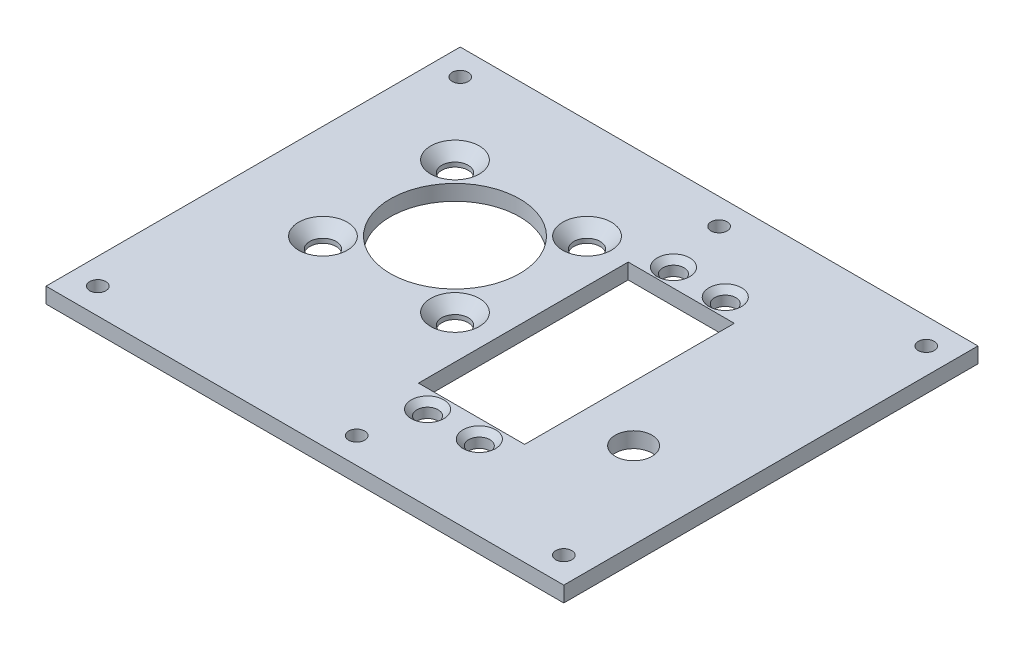
SolidWorks part; units mm, degrees
ref_plane "Płaszczyzna przednia" through (0, 0, 0) normal (0, 0, 1) x (1, 0, 0)
ref_plane "Płaszczyzna górna" through (0, 0, 0) normal (0, 1, 0) x (1, 0, 0)
ref_plane "Płaszczyzna prawa" through (0, 0, 0) normal (1, 0, 0) x (0, 0, -1)
sketch "Szkic1" plane through (0, 0, 0) normal (0, 1, 0) x (1, 0, 0)
  line L6 (-20.2688, 11.7569) -> (5.2312, -13.7431) construction
  line L11 (-38.6633, 31.161) -> (61.3367, 31.161)
  line L12 (-38.6633, 31.161) -> (-38.6633, -48.839)
  line L13 (-38.6633, -48.839) -> (61.3367, -48.839)
  line L14 (61.3367, 31.161) -> (61.3367, -48.839)
  line L15 (-20.2688, -13.7431) -> (5.2312, 11.7569) construction
  line L17 (13.5251, 11.411) -> (34.0251, 11.411)
  line L18 (13.5251, 11.411) -> (13.5251, -29.089)
  line L23 (13.5251, -29.089) -> (34.0251, -29.089)
  line L24 (34.0251, 11.411) -> (34.0251, -29.089)
  circle A0 centre (-7.5188, -0.9931) radius 12.5
  circle A2 centre (-20.2688, 11.7569) radius 2.55
  circle A3 centre (5.2312, 11.7569) radius 2.55
  circle A4 centre (5.2312, -13.7431) radius 2.55
  circle A5 centre (-20.2688, -13.7431) radius 2.55
  circle A6 centre (18.7751, 14.911) radius 2.05
  circle A7 centre (28.7751, 14.911) radius 2.05
  circle A8 centre (18.7751, -32.589) radius 2.05
  circle A9 centre (28.7751, -32.589) radius 2.05
  circle A10 centre (23.7751, -18.789) radius 0.5
  circle A11 centre (-7.5188, -0.9931) radius 0.5
  circle A12 centre (44.7751, -18.789) radius 3.55
  circle A13 centre (44.7751, -18.789) radius 0.5
  circle A14 centre (-33.6633, 26.161) radius 1.55
  circle A15 centre (56.3367, 26.161) radius 1.55
  circle A16 centre (56.3367, -43.839) radius 1.55
  circle A17 centre (-33.6633, -43.839) radius 1.55
  circle A18 centre (16.3367, 26.161) radius 1.55
  circle A19 centre (16.3367, -43.839) radius 1.55
  point P18 (23.7751, -29.089)
  point P22 (23.7751, 11.411)
  point P27 (11.3367, -8.839)
  dimension "D3" = 10.3
  dimension "D5" = 3.5
  dimension "D13" = 36
  dimension "D18" = 19.75
  dimension "D20" = 5.1
  dimension "D22" = 25
  dimension "D23" = 7.1
  dimension "D24" = 4.1
  dimension "D25" = 47.5
  dimension "D26" = 37.5616
  dimension "D1" = 100
  dimension "D2" = 80
  dimension "D4" = 10.25
  dimension "D6" = 3.5
  dimension "D7" = 5
  dimension "D8" = 5
  dimension "D9" = 3.5
  dimension "D10" = 3.5
  dimension "D11" = 5
  dimension "D12" = 5
  dimension "D14" = 21
  dimension "D15" = 40.5
  dimension "D16" = 20.5
  dimension "D17" = 10.3
  dimension "D19" = 19.75
  dimension "D21" = 25.5
  dimension "D27" = 30.05
extrude "Dodanie-wyciągnięcie1" add sketch "Szkic1" along normal blind 3 contours L14 L11 L12 L13 A12 A9 A8 A7 A6 A5 A4 A3 A2 A0 L17 L24 L23 L18 region at (11.0911, 0, 9.4735)
sketch "Sketch1" plane through (0, 0, 0) normal (0, 1, 0) x (1, 0, 0)
  point P0 (-20.2688, -13.7431)
  point P3 (5.2312, -13.7431)
  point P6 (5.2312, 11.7569)
  point P9 (-20.2688, 11.7569)
sketch "Sketch3" plane through (0, 3, 0) normal (0, 1, 0) x (1, 0, 0)
  point P0 (-20.2688, -13.7431)
  point P3 (5.2312, -13.7431)
  point P6 (5.2312, 11.7569)
  point P9 (-20.2688, 11.7569)
hole_wizard "CSK for M4 Countersunk Flat Head Screw1" positions "Sketch3" profile "Sketch4" countersink size "M4" standard "ISO" end condition through all
sketch "Sketch4" plane through (-20.2688, 3, 13.7431) normal (1, 0, 0) x (0, 0, 1)
  line L0 (0, 0) -> (0, 3)
  line L1 (0, 3) -> (2.25, 3)
  line L2 (2.25, 3) -> (2.25, 2.45)
  line L3 (2.25, 2.45) -> (4.7, 0)
  line L5 (4.7, 0) -> (0, 0)
  line L6 (-2.25, 2.45) -> (-4.7, 0) construction
  line L11 (0, -6.35) -> (0, 107.95) construction
  dimension "Thru Hole Dia." = 4.5
  dimension "Thru Hole Depth" = 3
  dimension "Near C'Sink Dia." = 9.4
  dimension "Near C'Sink Angle" = 90
sketch "Sketch5" plane through (0, 3, 0) normal (0, 1, 0) x (1, 0, 0)
  point P0 (18.7751, 14.911)
  point P3 (28.7751, 14.911)
  point P6 (18.7751, -32.589)
  point P9 (28.7751, -32.589)
hole_wizard "CSK for M3 Countersunk Flat Head Screw1" positions "Sketch5" profile "Sketch6" countersink size "M3" standard "ISO" end condition through all
sketch "Sketch6" plane through (18.7751, 3, -14.911) normal (1, 0, 0) x (0, 0, 1)
  line L0 (0, 0) -> (0, 3)
  line L1 (0, 3) -> (1.7, 3)
  line L2 (1.7, 3) -> (1.7, 1.45)
  line L3 (1.7, 1.45) -> (3.15, 0)
  line L5 (3.15, 0) -> (0, 0)
  line L6 (-1.7, 1.45) -> (-3.15, 0) construction
  line L11 (0, -6.35) -> (0, 107.95) construction
  dimension "Thru Hole Dia." = 3.4
  dimension "Thru Hole Depth" = 3
  dimension "Near C'Sink Dia." = 6.3
  dimension "Near C'Sink Angle" = 90
